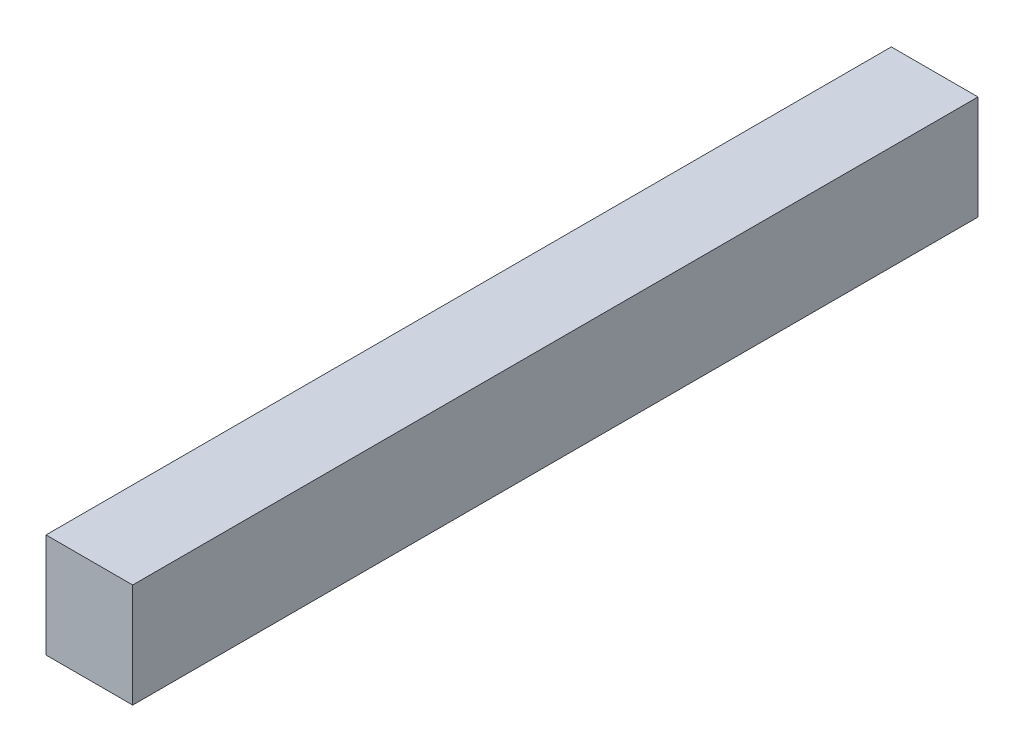
SolidWorks part; units mm, degrees
ref_plane "Front Plane" through (0, 0, 0) normal (0, 0, 1) x (1, 0, 0)
ref_plane "Top Plane" through (0, 0, 0) normal (0, 1, 0) x (1, 0, 0)
ref_plane "Right Plane" through (0, 0, 0) normal (1, 0, 0) x (0, 0, -1)
sketch "Sketch1" plane through (0, 0, 0) normal (0, 0, 1) x (1, 0, 0)
  line L1 (-1, 1.2) -> (1, 1.2)
  line L2 (-1, 1.2) -> (-1, -1.2)
  line L3 (-1, -1.2) -> (1, -1.2)
  line L4 (1, 1.2) -> (1, -1.2)
  line L5 (-1, 1.2) -> (1, -1.2) construction
  line L6 (-1, -1.2) -> (1, 1.2) construction
  point P0 (0, 0)
  point P6 (0, 0)
  dimension "D1" = 2
  dimension "D2" = 2.4
extrude "Boss-Extrude1" add sketch "Sketch1" along normal blind 19.5 contours L4 L3 L2 L1
